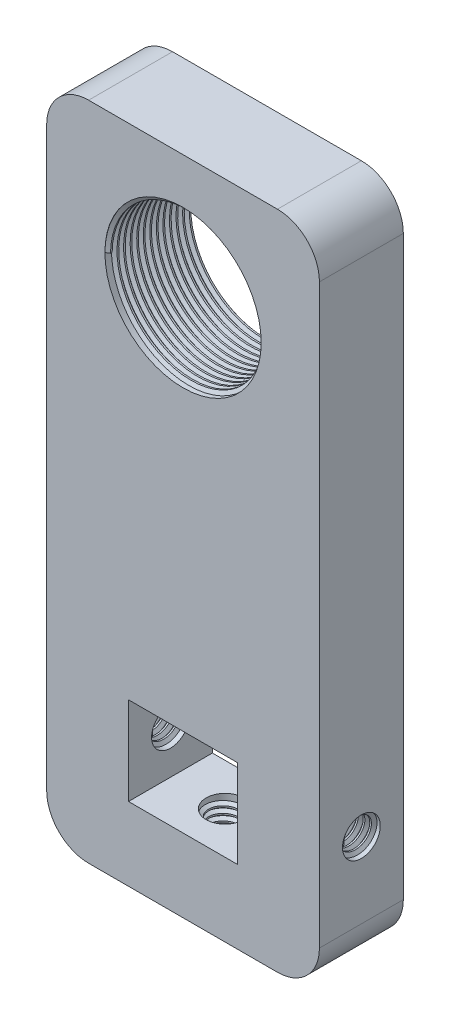
SolidWorks part; units mm, degrees
ref_plane "Front Plane" through (0, 0, 0) normal (0, 0, 1) x (1, 0, 0)
ref_plane "Top Plane" through (0, 0, 0) normal (0, 1, 0) x (1, 0, 0)
ref_plane "Right Plane" through (0, 0, 0) normal (1, 0, 0) x (0, 0, -1)
sketch "Sketch1" plane through (0, 0, 0) normal (0, 0, 1) x (1, 0, 0)
  line L2 (0, 0) -> (0, 66.04)
  line L3 (5.08, 71.12) -> (27.94, 71.12)
  line L4 (33.02, 0) -> (33.02, 66.04)
  line L5 (9.906, 0) -> (9.906, 10.668)
  line L6 (9.906, 10.668) -> (23.114, 10.668)
  line L7 (23.114, 10.668) -> (23.114, 0)
  line L11 (0, 0) -> (0, -3.81)
  line L12 (5.08, -8.89) -> (27.94, -8.89)
  line L13 (33.02, -3.81) -> (33.02, 0)
  line L14 (9.906, 0) -> (23.114, 0)
  line L15 (16.51, 71.12) -> (16.51, 56.134) construction
  line L16 (16.51, 56.134) -> (16.51, 25.654) construction
  line L17 (16.51, 10.668) -> (16.51, 25.654) construction
  line L18 (16.51, 0) -> (16.51, -8.89) construction
  line L19 (0, 10.668) -> (33.02, 10.668) construction
  arc A3 (0, -3.81) -> (5.08, -8.89) centre (5.08, -3.81) ccw
  arc A4 (27.94, -8.89) -> (33.02, -3.81) centre (27.94, -3.81) ccw
  arc A5 (27.94, 71.12) -> (33.02, 66.04) centre (27.94, 66.04) cw
  arc A6 (0, 66.04) -> (5.08, 71.12) centre (5.08, 66.04) cw
  circle A8 centre (16.51, 56.134) radius 9.4615
  point P16 (16.51, 71.12)
  point P27 (0, 71.12)
  dimension "D5" = 18.923
  dimension "D7" = 5.08
  dimension "D1" = 13.208
  dimension "D2" = 71.12
  dimension "D3" = 10.668
  dimension "D4" = 8.89
  dimension "D8" = 33.02
extrude "Boss-Extrude2" add sketch "Sketch1" along normal blind 10.16
sketch "Sketch4" plane through (0, 0, 0) normal (-1, 0, 0) x (0, 0, 1)
  circle A0 centre (5.08, 5.334) radius 2.286
  dimension "D1" = 4.572
  dimension "D2" = 5.334
extrude "Cut-Extrude1" cut sketch "Sketch4" against normal blind 38.1
sketch "Sketch6" plane through (0, -8.89, 0) normal (0, -1, 0) x (1, 0, 0)
  line L0 (16.51, 5.08) -> (16.51, 10.16) construction
  line L1 (5.08, 10.16) -> (27.94, 10.16) construction
  line L2 (16.51, 5.08) -> (27.94, 5.08) construction
  line L3 (27.94, 10.16) -> (27.94, 0) construction
  circle A0 centre (16.51, 5.08) radius 2.286
  dimension "D1" = 4.572
extrude "Cut-Extrude2" cut sketch "Sketch6" against normal blind 10.16
thread "Thread1" pitch 0.7937 method extrude profile "Thread Profile1" start angle 0, offset 0, length 9.652, pitch 0.7937, diameter 18.923
ref_plane "Plane1" through (7.0485, 56.134, 10.16) normal (0, -1, 0) x (-1, 0, 0)
sketch "Thread Profile1" plane through (7.0485, 56.134, 10.16) normal (0, -1, 0) x (-1, 0, 0)
  line L0 (0, 0) -> (0, 0.7937) construction
  line L11 (0, 0) -> (0, 0.6945)
  line L12 (0, 0.6945) -> (-0.4296, 0.4465)
  line L13 (-0.4296, 0.4465) -> (-0.4296, 0.248)
  line L15 (-0.4296, 0.248) -> (0, 0)
  line L17 (-0.4296, 0.3473) -> (0, 0.3473) construction
  point P2 (0, 0)
  dimension "Pitch" = 0.7937
  dimension "Profile_Angle" = 60
  dimension "Profile_Land" = 0.1984
  dimension "Profile_Height" = 0.4296
thread "Thread2" pitch 0.7937 method extrude profile "Thread Profile2" start angle 0, offset 0, length 9.144, pitch 0.7937, diameter 4.572
ref_plane "Plane2" through (0, 5.334, 2.794) normal (0, -1, 0) x (0, 0, -1)
sketch "Thread Profile2" plane through (0, 5.334, 2.794) normal (0, -1, 0) x (0, 0, -1)
  line L0 (0, 0) -> (0, 0.7937) construction
  line L11 (0, 0) -> (0, 0.6945)
  line L12 (0, 0.6945) -> (-0.4296, 0.4465)
  line L13 (-0.4296, 0.4465) -> (-0.4296, 0.248)
  line L15 (-0.4296, 0.248) -> (0, 0)
  line L17 (-0.4296, 0.3473) -> (0, 0.3473) construction
  point P2 (0, 0)
  dimension "Pitch" = 0.7937
  dimension "Profile_Angle" = 60
  dimension "Profile_Land" = 0.1984
  dimension "Profile_Height" = 0.4296
thread "Thread3" pitch 0.7937 method extrude profile "Thread Profile3" start angle 0, offset 0, length 9.144, pitch 0.7937, diameter 4.572
ref_plane "Plane3" through (33.02, 5.334, 7.366) normal (0, -1, 0) x (0, 0, 1)
sketch "Thread Profile3" plane through (33.02, 5.334, 7.366) normal (0, -1, 0) x (0, 0, 1)
  line L0 (0, 0) -> (0, 0.7937) construction
  line L11 (0, 0) -> (0, 0.6945)
  line L12 (0, 0.6945) -> (-0.4296, 0.4465)
  line L13 (-0.4296, 0.4465) -> (-0.4296, 0.248)
  line L15 (-0.4296, 0.248) -> (0, 0)
  line L17 (-0.4296, 0.3473) -> (0, 0.3473) construction
  point P2 (0, 0)
  dimension "Pitch" = 0.7937
  dimension "Profile_Angle" = 60
  dimension "Profile_Land" = 0.1984
  dimension "Profile_Height" = 0.4296
thread "Thread4" pitch 0.7937 method extrude profile "Thread Profile4" start angle 0, offset 0, length 8.128, pitch 0.7937, diameter 4.572
ref_plane "Plane4" through (18.796, -8.89, 5.08) normal (0, 0, 1) x (1, 0, 0)
sketch "Thread Profile4" plane through (18.796, -8.89, 5.08) normal (0, 0, 1) x (1, 0, 0)
  line L0 (0, 0) -> (0, 0.7937) construction
  line L11 (0, 0) -> (0, 0.6945)
  line L12 (0, 0.6945) -> (-0.4296, 0.4465)
  line L13 (-0.4296, 0.4465) -> (-0.4296, 0.248)
  line L15 (-0.4296, 0.248) -> (0, 0)
  line L17 (-0.4296, 0.3473) -> (0, 0.3473) construction
  point P2 (0, 0)
  dimension "Pitch" = 0.7937
  dimension "Profile_Angle" = 60
  dimension "Profile_Land" = 0.1984
  dimension "Profile_Height" = 0.4296
